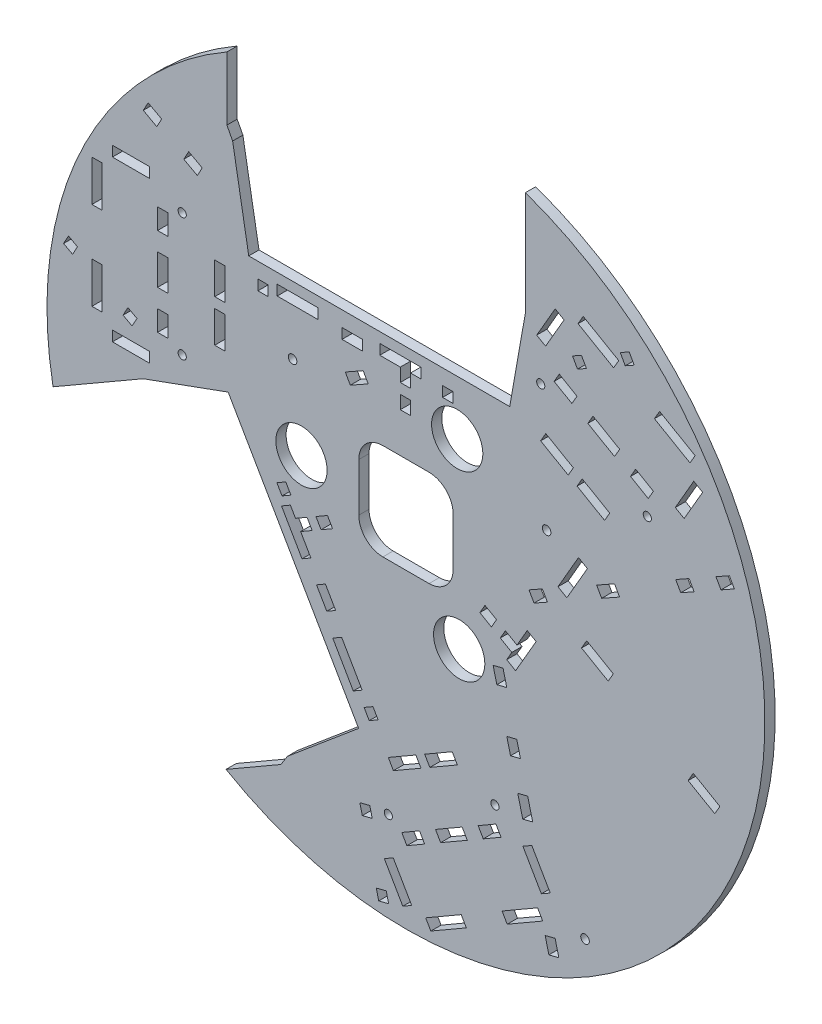
SolidWorks part; units mm, degrees
material "Balsa"
ref_plane "Plan de face" through (0, 0, 0) normal (0, 0, 1) x (1, 0, 0)
ref_plane "Plan de dessus" through (0, 0, 0) normal (0, 1, 0) x (1, 0, 0)
ref_plane "Plan de droite" through (0, 0, 0) normal (1, 0, 0) x (0, 0, -1)
sketch "Esquisse1" plane through (0, 0, 0) normal (0, 0, 1) x (1, 0, 0)
  circle A0 centre (148.0804, -12.1102) radius 175
  dimension "D1" = 350
extrude "Boss.-Extru.1" add sketch "Esquisse1" along normal blind 5
sketch "Esquisse2" plane through (0, 0, 5) normal (0, 0, 1) x (1, 0, 0)
  line L0 (135.3118, 53.7774) -> (135.3118, 48.7774)
  line L1 (5, 72.2774) -> (23, 72.2774)
  line L2 (5, 72.2774) -> (5, 67.2774)
  line L3 (5, 67.2774) -> (23, 67.2774)
  line L4 (23, 72.2774) -> (23, 67.2774)
  line L5 (-5, 62.2774) -> (0, 62.2774)
  line L6 (-5, 62.2774) -> (-5, 42.2774)
  line L7 (-5, 42.2774) -> (0, 42.2774)
  line L8 (0, 62.2774) -> (0, 42.2774)
  line L9 (-5, 19.2774) -> (0, 19.2774)
  line L10 (-5, 19.2774) -> (-5, -0.7226)
  line L11 (-5, -0.7226) -> (0, -0.7226)
  line L12 (0, 19.2774) -> (0, -0.7226)
  line L13 (5, -5.7226) -> (23, -5.7226)
  line L14 (5, -5.7226) -> (5, -10.7226)
  line L15 (5, -10.7226) -> (23, -10.7226)
  line L16 (23, -5.7226) -> (23, -10.7226)
  line L17 (27, 14.2774) -> (32, 14.2774)
  line L18 (27, 14.2774) -> (27, 4.2774)
  line L19 (27, 4.2774) -> (32, 4.2774)
  line L20 (32, 14.2774) -> (32, 4.2774)
  line L21 (27, 38.2774) -> (32, 38.2774)
  line L22 (27, 38.2774) -> (27, 23.2774)
  line L23 (27, 23.2774) -> (32, 23.2774)
  line L24 (32, 38.2774) -> (32, 23.2774)
  line L25 (27, 57.2774) -> (32, 57.2774)
  line L26 (27, 57.2774) -> (27, 47.2774)
  line L27 (27, 47.2774) -> (32, 47.2774)
  line L28 (32, 57.2774) -> (32, 47.2774)
  line L29 (54.86, 48.7774) -> (59.86, 48.7774)
  line L30 (54.86, 48.7774) -> (54.86, 33.2774)
  line L31 (54.86, 33.2774) -> (59.86, 33.2774)
  line L32 (59.86, 48.7774) -> (59.86, 33.2774)
  line L33 (54.86, 28.2774) -> (59.86, 28.2774)
  line L34 (54.86, 28.2774) -> (54.86, 12.7774)
  line L35 (54.86, 12.7774) -> (59.86, 12.7774)
  line L36 (59.86, 28.2774) -> (59.86, 12.7774)
  line L37 (85.3118, 53.7774) -> (105.3118, 53.7774)
  line L38 (85.3118, 53.7774) -> (85.3118, 48.7774)
  line L39 (85.3118, 48.7774) -> (105.3118, 48.7774)
  line L40 (105.3118, 53.7774) -> (105.3118, 48.7774)
  line L41 (145.3118, 37.2774) -> (150.3118, 37.2774)
  line L42 (145.3118, 37.2774) -> (145.3118, 30.7774)
  line L43 (145.3118, 30.7774) -> (150.3118, 30.7774)
  line L44 (150.3118, 37.2774) -> (150.3118, 30.7774)
  line L45 (135.3118, 48.7774) -> (145.3118, 48.7774)
  line L46 (155.3118, 48.7774) -> (135.3118, 48.7774) construction
  line L47 (145.3118, 48.7774) -> (145.3118, 42.2774)
  line L48 (145.3118, 42.2774) -> (150.3118, 42.2774)
  line L49 (150.3118, 42.2774) -> (150.3118, 48.7774)
  line L50 (150.3118, 48.7774) -> (155.3118, 48.7774)
  line L51 (155.3118, 48.7774) -> (155.3118, 53.7774)
  line L52 (155.3118, 53.7774) -> (135.3118, 53.7774)
  line L53 (292.7025, 69.6073) -> (283.7025, 54.0188)
  line L54 (292.7025, 69.6073) -> (288.3723, 72.1073)
  line L55 (288.3723, 72.1073) -> (279.3723, 56.5188)
  line L56 (283.7025, 54.0188) -> (279.3723, 56.5188)
  line L57 (289.0422, 83.2676) -> (286.5422, 78.9374)
  line L58 (289.0422, 83.2676) -> (271.7217, 93.2676)
  line L59 (271.7217, 93.2676) -> (269.2217, 88.9374)
  line L60 (286.5422, 78.9374) -> (269.2217, 88.9374)
  line L61 (251.8031, 104.7676) -> (249.3031, 100.4374)
  line L62 (251.8031, 104.7676) -> (234.4826, 114.7676)
  line L63 (234.4826, 114.7676) -> (231.9826, 110.4374)
  line L64 (249.3031, 100.4374) -> (231.9826, 110.4374)
  line L65 (225.1525, 108.6073) -> (216.1525, 93.0188)
  line L66 (225.1525, 108.6073) -> (220.8223, 111.1073)
  line L67 (220.8223, 111.1073) -> (211.8223, 95.5188)
  line L68 (216.1525, 93.0188) -> (211.8223, 95.5188)
  line L69 (231.473, 79.5547) -> (228.973, 75.2246)
  line L70 (231.473, 79.5547) -> (222.8127, 84.5547)
  line L71 (222.8127, 84.5547) -> (220.3127, 80.2246)
  line L72 (228.973, 75.2246) -> (220.3127, 80.2246)
  line L73 (252.2576, 67.5547) -> (249.7576, 63.2246)
  line L74 (252.2576, 67.5547) -> (239.2672, 75.0547)
  line L75 (239.2672, 75.0547) -> (236.7672, 70.7246)
  line L76 (249.7576, 63.2246) -> (236.7672, 70.7246)
  line L77 (268.7121, 58.0547) -> (266.2121, 53.7246)
  line L78 (268.7121, 58.0547) -> (260.0518, 63.0547)
  line L79 (260.0518, 63.0547) -> (257.5518, 58.7246)
  line L80 (266.2121, 53.7246) -> (257.5518, 58.7246)
  line L81 (247.4209, 38.1773) -> (244.9209, 33.8472)
  line L82 (247.4209, 38.1773) -> (233.9975, 45.9273)
  line L83 (233.9975, 45.9273) -> (231.4975, 41.5972)
  line L84 (244.9209, 33.8472) -> (231.4975, 41.5972)
  line L85 (229.6673, 48.4273) -> (227.1673, 44.0972)
  line L86 (229.6673, 48.4273) -> (216.2439, 56.1773)
  line L87 (216.2439, 56.1773) -> (213.7439, 51.8472)
  line L88 (227.1673, 44.0972) -> (213.7439, 51.8472)
  line L89 (211.5251, -33.996) -> (207.195, -31.496)
  line L90 (236.5251, 9.3053) -> (226.5251, -8.0153)
  line L91 (236.5251, 9.3053) -> (232.195, 11.8053)
  line L92 (232.195, 11.8053) -> (222.195, -5.5153)
  line L93 (226.5251, -8.0153) -> (222.195, -5.5153)
  line L94 (192.2357, -34.4063) -> (189.7357, -38.7364)
  line L95 (192.2357, -34.4063) -> (186.6065, -31.1563)
  line L96 (186.6065, -31.1563) -> (184.1065, -35.4864)
  line L97 (189.7357, -38.7364) -> (184.1065, -35.4864)
  line L98 (207.195, -31.496) -> (202.195, -40.1563)
  line L99 (202.195, -40.1563) -> (196.5658, -36.9063)
  line L100 (196.5658, -36.9063) -> (194.0658, -41.2364)
  line L101 (194.0658, -41.2364) -> (199.695, -44.4864)
  line L102 (199.695, -44.4864) -> (197.195, -48.8165)
  line L103 (197.195, -48.8165) -> (201.5251, -51.3165)
  line L104 (201.5251, -51.3165) -> (211.5251, -33.996)
  line L105 (146.5388, -178.2153) -> (137.5388, -162.6268)
  line L106 (146.5388, -178.2153) -> (150.869, -175.7153)
  line L107 (150.869, -175.7153) -> (141.869, -160.1268)
  line L108 (137.5388, -162.6268) -> (141.869, -160.1268)
  line L109 (160.1991, -181.8755) -> (157.6991, -177.5454)
  line L110 (160.1991, -181.8755) -> (177.5196, -171.8755)
  line L111 (177.5196, -171.8755) -> (175.0196, -167.5454)
  line L112 (157.6991, -177.5454) -> (175.0196, -167.5454)
  line L113 (197.4382, -160.3755) -> (194.9382, -156.0454)
  line L114 (197.4382, -160.3755) -> (214.7587, -150.3755)
  line L115 (214.7587, -150.3755) -> (212.2587, -146.0454)
  line L116 (194.9382, -156.0454) -> (212.2587, -146.0454)
  line L117 (214.0888, -139.2153) -> (205.0888, -123.6268)
  line L118 (214.0888, -139.2153) -> (218.4189, -136.7153)
  line L119 (218.4189, -136.7153) -> (209.4189, -121.1268)
  line L120 (205.0888, -123.6268) -> (209.4189, -121.1268)
  line L121 (185.7683, -130.1627) -> (183.2683, -125.8326)
  line L122 (185.7683, -130.1627) -> (194.4286, -125.1627)
  line L123 (194.4286, -125.1627) -> (191.9286, -120.8326)
  line L124 (183.2683, -125.8326) -> (191.9286, -120.8326)
  line L125 (164.9837, -142.1627) -> (162.4837, -137.8326)
  line L126 (164.9837, -142.1627) -> (177.9741, -134.6627)
  line L127 (177.9741, -134.6627) -> (175.4741, -130.3326)
  line L128 (162.4837, -137.8326) -> (175.4741, -130.3326)
  line L129 (148.5292, -151.6627) -> (146.0292, -147.3326)
  line L130 (148.5292, -151.6627) -> (157.1895, -146.6627)
  line L131 (157.1895, -146.6627) -> (154.6895, -142.3326)
  line L132 (146.0292, -147.3326) -> (154.6895, -142.3326)
  line L133 (141.9604, -123.2852) -> (139.4604, -118.9551)
  line L134 (141.9604, -123.2852) -> (155.3838, -115.5352)
  line L135 (155.3838, -115.5352) -> (152.8838, -111.2051)
  line L136 (139.4604, -118.9551) -> (152.8838, -111.2051)
  line L137 (159.7139, -113.0352) -> (157.2139, -108.7051)
  line L138 (159.7139, -113.0352) -> (173.1373, -105.2852)
  line L139 (173.1373, -105.2852) -> (170.6373, -100.9551)
  line L140 (157.2139, -108.7051) -> (170.6373, -100.9551)
  line L141 (97.4044, -56.1119) -> (101.7345, -53.6119)
  line L142 (122.4044, -99.4132) -> (112.4044, -82.0927)
  line L143 (122.4044, -99.4132) -> (126.7345, -96.9132)
  line L144 (126.7345, -96.9132) -> (116.7345, -79.5927)
  line L145 (112.4044, -82.0927) -> (116.7345, -79.5927)
  line L146 (106.6938, -39.2017) -> (104.1938, -34.8716)
  line L147 (106.6938, -39.2017) -> (112.323, -35.9517)
  line L148 (112.323, -35.9517) -> (109.823, -31.6216)
  line L149 (104.1938, -34.8716) -> (109.823, -31.6216)
  line L150 (101.7345, -53.6119) -> (96.7345, -44.9517)
  line L151 (96.7345, -44.9517) -> (102.3637, -41.7017)
  line L152 (102.3637, -41.7017) -> (99.8637, -37.3716)
  line L153 (99.8637, -37.3716) -> (94.2345, -40.6216)
  line L154 (94.2345, -40.6216) -> (91.7345, -36.2914)
  line L155 (91.7345, -36.2914) -> (87.4044, -38.7914)
  line L156 (87.4044, -38.7914) -> (97.4044, -56.1119)
  line L157 (135.3118, 53.7774) -> (135.3118, 48.7774) construction
  line L158 (105.3118, 53.7774) -> (135.3118, 53.7774) construction
  point P83 (148.0804, -12.1102)
  point P192 (148.0804, -12.1102)
  point P193 (148.0804, -12.1102)
  dimension "D1" = 3
extrude "Enlèv. mat.-Extru.1" cut sketch "Esquisse2" against normal blind 5
sketch "Esquisse6" plane through (0, 0, 5) normal (0, 0, 1) x (1, 0, 0)
  line L0 (93.9998, -7.2151) -> (100.2998, -18.127) construction
  line L1 (206.3213, 102.2219) -> (206.3213, 185.5637)
  line L2 (125.0804, -35.6102) -> (171.0804, -35.6102) construction
  line L3 (125.0804, -35.6102) -> (125.0804, 11.3898) construction
  line L4 (125.0804, 11.3898) -> (171.0804, 11.3898) construction
  line L5 (171.0804, -35.6102) -> (171.0804, 11.3898) construction
  line L6 (125.0804, -35.6102) -> (171.0804, 11.3898) construction
  line L7 (125.0804, 11.3898) -> (171.0804, -35.6102) construction
  line L8 (206.3213, 185.5637) -> (60.7972, 185.5637)
  line L9 (71.4438, 58.7774) -> (63.5848, 103.3483)
  line L10 (71.4438, 58.7774) -> (198.6608, 58.7774)
  line L11 (198.6608, 58.7774) -> (206.3213, 102.2219)
  line L12 (60.7972, 185.5637) -> (60.7972, 108.6824)
  line L13 (19.9456, -18.8381) -> (-52.2306, -60.5091)
  line L14 (-52.2306, -60.5091) -> (20.5314, -186.5366)
  line L15 (63.5848, 103.3483) -> (60.7972, 108.6824)
  line L16 (125.0083, -113.9232) -> (90.3383, -143.0148)
  line L17 (125.0083, -113.9232) -> (61.3998, -3.7501)
  line L18 (61.3998, -3.7501) -> (19.9456, -18.8381)
  line L19 (136.8304, -23.8602) -> (159.3304, -23.8602) construction
  line L20 (236.1714, -21.3074) -> (249.1617, -28.8074)
  line L21 (236.1714, -21.3074) -> (233.6714, -25.6375)
  line L22 (249.1617, -28.8074) -> (246.6617, -33.1375)
  line L23 (233.6714, -25.6375) -> (246.6617, -33.1375)
  line L24 (288.1329, -51.3074) -> (301.1233, -58.8074)
  line L25 (288.1329, -51.3074) -> (285.6329, -55.6375)
  line L26 (301.1233, -58.8074) -> (298.6233, -63.1375)
  line L27 (285.6329, -55.6375) -> (298.6233, -63.1375)
  line L28 (226.5251, -8.0153) -> (236.5251, 9.3053) construction
  line L29 (279.3723, 56.5188) -> (283.7025, 54.0188) construction
  line L30 (136.8304, -0.3602) -> (159.3304, -0.3602) construction
  line L31 (64.5427, 103.6743) -> (63.0102, 106.6067) construction
  line L32 (20.5314, -186.5366) -> (87.1126, -148.0959)
  line L33 (90.3383, -143.0148) -> (87.1126, -148.0959)
  line L34 (125.0804, -23.8602) -> (125.0804, -0.3602)
  line L35 (136.8304, -35.6102) -> (159.3304, -35.6102)
  line L36 (159.3304, -35.6102) -> (159.6478, -35.9264)
  line L37 (171.0804, -23.8602) -> (171.0804, -0.3602)
  line L38 (159.3304, 11.3898) -> (136.8304, 11.3898)
  circle A0 centre (173.06, 32.2774) radius 12.5
  circle A1 centre (174.0314, -55.9369) radius 12.5
  circle A2 centre (97.1498, -12.671) radius 12.5
  arc A3 (125.0804, -23.8602) -> (136.8304, -35.6102) centre (136.8304, -23.8602) ccw
  arc A4 (171.0804, -23.8602) -> (159.3304, -35.6102) centre (159.3304, -23.8602) cw
  arc A5 (171.0804, -0.3602) -> (159.3304, 11.3898) centre (159.3304, -0.3602) ccw
  arc A6 (125.0804, -0.3602) -> (136.8304, 11.3898) centre (136.8304, -0.3602) cw
  point P2 (148.0804, -12.1102)
  point P8 (148.0804, -12.1102)
  point P10 (148.0804, -12.1102)
  point P35 (148.0804, -12.1102)
  point P48 (148.0804, -12.1102)
  dimension "D12" = 25
  dimension "D23" = 11.75
  dimension "D3" = 47
  dimension "D4" = 46
  dimension "D5" = 70.8876
  dimension "D6" = 50.5804
  dimension "D7" = 127.217
  dimension "D8" = 100
  dimension "D9" = 100
  dimension "D10" = 145.5241
  dimension "D11" = 43.4444
  dimension "D13" = 5
  dimension "D14" = 15
  dimension "D15" = 15
  dimension "D16" = 45
  dimension "D17" = 15
  dimension "D18" = 89
  dimension "D19" = 2
  dimension "D20" = 1
  dimension "D21" = 11.75
  dimension "D22" = 11.75
  dimension "D1" = 3
extrude "Enlèv. mat.-Extru.6" cut sketch "Esquisse6" against normal blind 5 contours L33 L16 L17 L18 L13 L14 L32 | A2 | L15 L9 L10 L11 L1 L8 L12 | A6 L34 A3 L35 A4 L37 A5 L38 | A1 | A0 | L25 L27 L26 L24 | L21 L23 L22 L20 region at (134.0885, 123.3873, 5) region at (37.7321, -91.9763, 5) region at (241.4166, -27.2225, 5) region at (293.3781, -57.2225, 5) region at (148.0804, -12.1102, 5) region at (173.06, 32.2774, 5) region at (174.0314, -55.9369, 5) region at (97.1498, -12.671, 5)
hole_wizard "Trous de centrage Ø4.0mm1" positions "Esquisse7" profile "Esquisse8" hole size "Ø4.0" standard "Ansi Metric" end condition through all
sketch "Esquisse7" plane through (148.0804, -12.1102, -78) normal (0, 0, -1) x (1, 0, 0)
  point P0 (65.7012, -88.0226)
  point P3 (117.6627, -58.0226)
  point P6 (-109.0804, -72.8876)
  point P9 (-109.0804, -12.8876)
  point P12 (-8.5823, 130.9102)
  point P15 (43.3792, 100.9102)
sketch "Esquisse8" plane through (213.7816, 75.9124, -78) normal (1, 0, 0) x (0, 1, 0)
  line L0 (0, 0) -> (0, 83)
  line L1 (0, 83) -> (2, 83)
  line L2 (2, 83) -> (2, 0)
  line L3 (2, 0) -> (0, 0)
  line L4 (0, -6.35) -> (0, 107.95) construction
  dimension "Diamètre du perçage jusqu'au prochain" = 4
  dimension "Profondeur du perçage jusqu'au prochain" = 83
sketch "Esquisse9" plane through (0, 0, 5) normal (0, 0, 1) x (1, 0, 0)
  line L0 (301.6473, 32.8747) -> (299.2005, 37.2351)
  line L1 (301.6473, 32.8747) -> (308.1879, 36.5449)
  line L2 (299.2005, 37.2351) -> (305.7411, 40.9053)
  line L3 (308.1879, 36.5449) -> (305.7411, 40.9053)
  line L4 (282.0254, 21.8642) -> (279.5786, 26.2246)
  line L5 (282.0254, 21.8642) -> (288.566, 25.5344)
  line L6 (279.5786, 26.2246) -> (286.1192, 29.8948)
  line L7 (288.566, 25.5344) -> (286.1192, 29.8948)
  line L8 (252.2089, 5.133) -> (249.7621, 9.4935)
  line L9 (252.2089, 5.133) -> (243.488, 0.2395)
  line L10 (249.7621, 9.4935) -> (241.0412, 4.5999)
  line L11 (243.488, 0.2395) -> (241.0412, 4.5999)
  line L12 (214.6084, -10.2326) -> (217.0552, -14.593)
  line L13 (214.6084, -10.2326) -> (208.0678, -13.9027)
  line L14 (217.0552, -14.593) -> (210.5146, -18.2632)
  line L15 (208.0678, -13.9027) -> (210.5146, -18.2632)
  line L16 (217.0552, -14.593) -> (243.488, 0.2395) construction
  line L17 (214.6084, -10.2326) -> (217.0552, -14.593) construction
  line L18 (259.3473, 106.6065) -> (254.9869, 104.1597)
  line L19 (259.3473, 106.6065) -> (256.9005, 110.9669)
  line L20 (254.9869, 104.1597) -> (252.5401, 108.5201)
  line L21 (256.9005, 110.9669) -> (252.5401, 108.5201)
  line L22 (236.0696, 93.5445) -> (231.7091, 91.0977)
  line L23 (236.0696, 93.5445) -> (233.6228, 97.9049)
  line L24 (231.7091, 91.0977) -> (229.2624, 95.4581)
  line L25 (233.6228, 97.9049) -> (229.2624, 95.4581)
  line L26 (129.6754, 33.8428) -> (120.9546, 28.9492)
  line L27 (129.6754, 33.8428) -> (127.2286, 38.2032)
  line L28 (120.9546, 28.9492) -> (118.5078, 33.3096)
  line L29 (127.2286, 38.2032) -> (118.5078, 33.3096)
  line L30 (259.3473, 106.6065) -> (120.9546, 28.9492) construction
  line L31 (301.6473, 32.8747) -> (217.0552, -14.593) construction
  line L32 (-16.4384, 23.2791) -> (-12.0459, 20.8904)
  line L33 (-16.4384, 23.2791) -> (-18.8272, 18.8866)
  line L34 (-12.0459, 20.8904) -> (-14.4347, 16.4979)
  line L35 (-18.8272, 18.8866) -> (-14.4347, 16.4979)
  line L36 (12.552, 7.5136) -> (16.9445, 5.1249)
  line L37 (12.552, 7.5136) -> (10.1633, 3.1211)
  line L38 (16.9445, 5.1249) -> (14.5558, 0.7324)
  line L39 (10.1633, 3.1211) -> (14.5558, 0.7324)
  line L42 (-26.9196, -12.1102) -> (148.0804, -12.1102) construction
  line L44 (22.4127, 98.9071) -> (29.0015, 95.324)
  line L45 (22.4127, 98.9071) -> (20.024, 94.5146)
  line L46 (29.0015, 95.324) -> (26.6128, 90.9315)
  line L47 (20.024, 94.5146) -> (26.6128, 90.9315)
  line L48 (42.179, 88.1579) -> (48.7677, 84.5748)
  line L49 (42.179, 88.1579) -> (39.7903, 83.7654)
  line L50 (48.7677, 84.5748) -> (46.379, 80.1823)
  line L51 (39.7903, 83.7654) -> (46.379, 80.1823)
  line L53 (148.0804, -12.1102) -> (9.6568, -109.2191) construction
  line L55 (129.7636, 187.6323) -> (148.0804, -12.1102) construction
  circle A0 centre (148.0804, -12.1102) radius 175 construction
  line B0 (154.106, -73.5915) -> (185.6214, -199.5155) construction
  line B1 (126.7996, -149.8343) -> (125.5857, -144.9839)
  line B2 (130.4361, -143.77) -> (125.5857, -144.9839)
  line B3 (131.65, -148.6204) -> (126.7996, -149.8343)
  line B4 (131.65, -148.6204) -> (130.4361, -143.77)
  line B5 (134.8115, -181.8469) -> (133.5976, -176.9965)
  line B6 (138.448, -175.7826) -> (133.5976, -176.9965)
  line B7 (139.6619, -180.633) -> (134.8115, -181.8469)
  line B8 (139.6619, -180.633) -> (138.448, -175.7826)
  line B9 (190.562, -54.5014) -> (195.4124, -53.2875)
  line B10 (197.2333, -60.5631) -> (195.4124, -53.2875)
  line B11 (192.3829, -61.777) -> (190.562, -54.5014)
  line B12 (192.3829, -61.777) -> (197.2333, -60.5631)
  line B13 (202.089, -79.9647) -> (197.2386, -81.1786)
  line B14 (199.0595, -88.4542) -> (197.2386, -81.1786)
  line B15 (203.9099, -87.2403) -> (202.089, -79.9647)
  line B16 (203.9099, -87.2403) -> (199.0595, -88.4542)
  line B17 (222.6043, -161.9364) -> (217.7539, -163.1503)
  line B18 (215.933, -155.8747) -> (217.7539, -163.1503)
  line B19 (220.7834, -154.6608) -> (222.6043, -161.9364)
  line B20 (220.7834, -154.6608) -> (215.933, -155.8747)
  dimension "D9" = 170.2546
  dimension "D1" = 10
  dimension "D2" = 5
  dimension "D3" = 7.5
  dimension "D4" = 10
  dimension "D5" = 7.5
  dimension "D6" = 7.5
  dimension "D7" = 5
  dimension "D8" = 117
  dimension "D10" = 167.3371
  dimension "D11" = 69
  dimension "D12" = 35.051
  dimension "D13" = 30.31
  dimension "D14" = 5
sketch_block_instance "Bloc1-1"
sketch_block "Bloc1"
extrude "Holes catchers of glass" cut sketch "Esquisse9" against normal blind 10
sketch "Esquisse10" plane through (0, 0, 5) normal (0, 0, 1) x (1, 0, 0)
  line L0 (89.4961, -27.6144) -> (91.9961, -31.9445)
  line L1 (89.4961, -27.6144) -> (85.1672, -30.1137)
  line L2 (91.9961, -31.9445) -> (87.6672, -34.4438)
  line L3 (85.1672, -30.1137) -> (87.6672, -34.4438)
  dimension "D1" = 4.9986
extrude "Holes boards servo" cut sketch "Esquisse10" against normal blind 10
sketch "Esquisse11" plane through (0, 0, 5) normal (0, 0, 1) x (1, 0, 0)
  line L0 (109.4829, -72.2325) -> (104.4829, -63.5722)
  line L1 (109.4829, -72.2325) -> (113.813, -69.7325)
  line L2 (104.4829, -63.5722) -> (108.813, -61.0722)
  line L3 (113.813, -69.7325) -> (108.813, -61.0722)
  line L4 (125.166, -99.3964) -> (108.8992, -71.2215) construction
  line L6 (116.7345, -79.5927) -> (112.4044, -82.0927) construction
  line L7 (130.166, -108.0567) -> (134.4961, -105.5567)
  line L8 (130.166, -108.0567) -> (127.666, -103.7266)
  line L9 (134.4961, -105.5567) -> (131.9961, -101.2266)
  line L10 (127.666, -103.7266) -> (131.9961, -101.2266)
  line L11 (207.4302, -101.3064) -> (209.8581, -111.0072)
  line L12 (170.9253, 51.2774) -> (165.9253, 51.2774)
  line L13 (170.9253, 51.2774) -> (170.9253, 46.2774)
  line L14 (170.9253, 46.2774) -> (165.9253, 46.2774)
  line L15 (165.9253, 51.2774) -> (165.9253, 46.2774)
  line L16 (126.9253, 51.2774) -> (116.9253, 51.2774)
  line L17 (126.9253, 51.2774) -> (126.9253, 46.2774)
  line L18 (126.9253, 46.2774) -> (116.9253, 46.2774)
  line L19 (116.9253, 51.2774) -> (116.9253, 46.2774)
  line L20 (80.9253, 51.2774) -> (75.9253, 51.2774)
  line L21 (80.9253, 51.2774) -> (80.9253, 46.2774)
  line L22 (80.9253, 46.2774) -> (75.9253, 46.2774)
  line L23 (75.9253, 51.2774) -> (75.9253, 46.2774)
  line L24 (207.4302, -101.3064) -> (202.5798, -102.5203)
  line L25 (209.8581, -111.0072) -> (205.0077, -112.2211)
  line L26 (202.5798, -102.5203) -> (205.0077, -112.2211)
  line L27 (203.9099, -87.2403) -> (202.089, -79.9647) construction
  line L28 (220.7834, -154.6608) -> (215.933, -155.8747) construction
  dimension "D1" = 10
  dimension "D2" = 10
  dimension "D3" = 5
  dimension "D4" = 5
  dimension "D5" = 5
  dimension "D6" = 10
  dimension "D7" = 45
extrude "Enlèv. mat.-Extru.7" cut sketch "Esquisse11" against normal blind 5
hole_wizard "Trou taraudé M51" positions "Esquisse12" profile "Esquisse13" tap size "M5" standard "ISO" end condition through all
sketch "Esquisse12" plane through (148.0804, -12.1102, 262) normal (0, 0, 1) x (-1, 0, 0)
  point P0 (-68.569, -27.6625)
  point P2 (55.2809, -37.9834)
  point P4 (-87.2993, 135.5593)
sketch "Esquisse13" plane through (216.6494, 15.5524, 262) normal (1, 0, 0) x (0, -1, 0)
  line L0 (0, 0) -> (0, 262)
  line L1 (0, 262) -> (2.1, 262)
  line L2 (2.1, 262) -> (2.1, 0)
  line L3 (2.1, 0) -> (0, 0)
  line L4 (0, -6.35) -> (0, 107.95) construction
  dimension "Diamètre principal du filetage" = 4.2
  dimension "Profondeur du trou pour taraudage jusqu'au prochain" = 262
